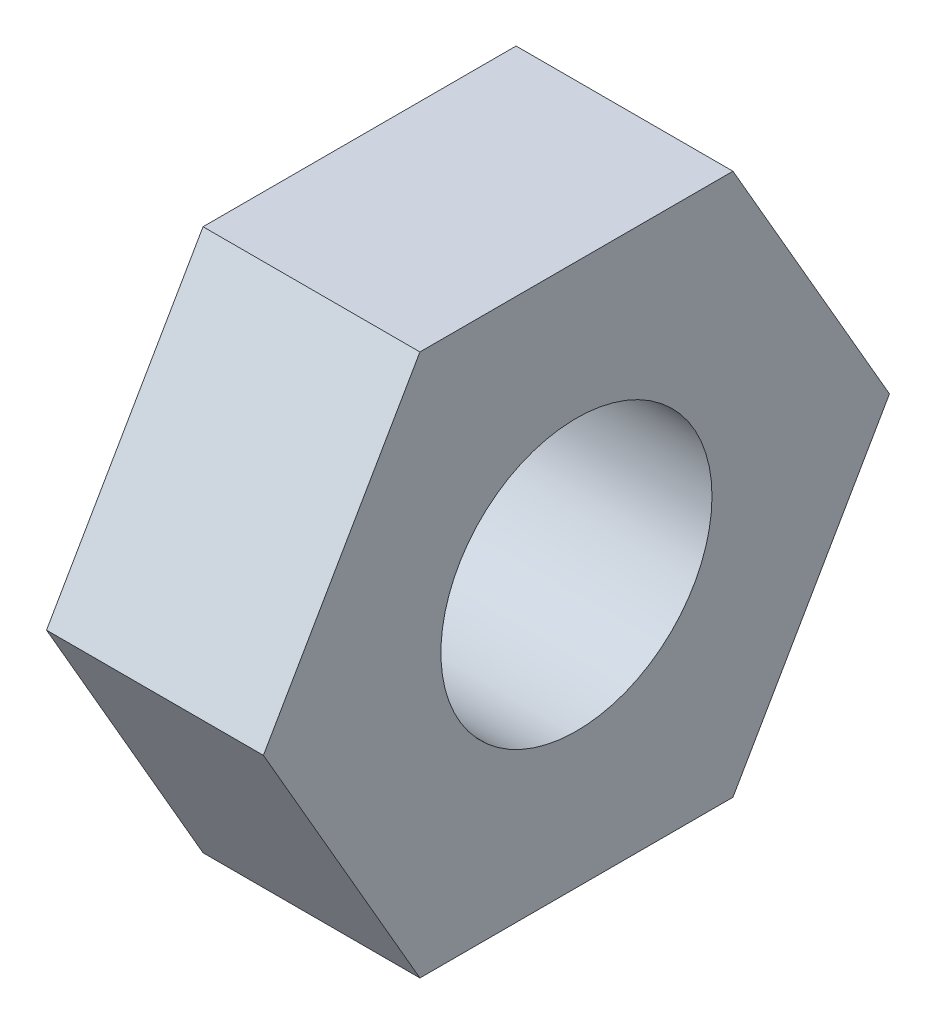
SolidWorks part; units mm, degrees
ref_plane "Front Plane" through (0, 0, 0) normal (0, 0, 1) x (1, 0, 0)
ref_plane "Top Plane" through (0, 0, 0) normal (0, 1, 0) x (1, 0, 0)
ref_plane "Right Plane" through (0, 0, 0) normal (1, 0, 0) x (0, 0, -1)
sketch "Nut Sketch" plane through (0, 0, 0) normal (1, 0, 0) x (0, 0, -1)
  line L0 (2.3094, 0) -> (1.1547, 2)
  line L1 (1.1547, 2) -> (-1.1547, 2)
  line L2 (-1.1547, 2) -> (-2.3094, 0)
  line L3 (-2.3094, 0) -> (-1.1547, -2)
  line L4 (-1.1547, -2) -> (1.1547, -2)
  line L5 (1.1547, -2) -> (2.3094, 0)
extrude "Nut" add sketch "Nut Sketch" along normal blind 1.6
ref_axis "Engine Axis" through (1.68, 0, 0) along (-1, 0, 0)
sketch "Thread Sketch" plane through (0, 0, 0) normal (0, 0, 1) x (1, 0, 0)
  line L0 (-1000, 0) -> (1000, 0) construction
  line L1 (-1, 0) -> (2.6, 0)
  line L2 (2.6, 0) -> (2.6, 1)
  line L3 (2.6, 1) -> (-1, 1)
  line L4 (-1, 1) -> (-1, 0)
revolve "Thread" cut sketch "Thread Sketch" angle 360 about L0
